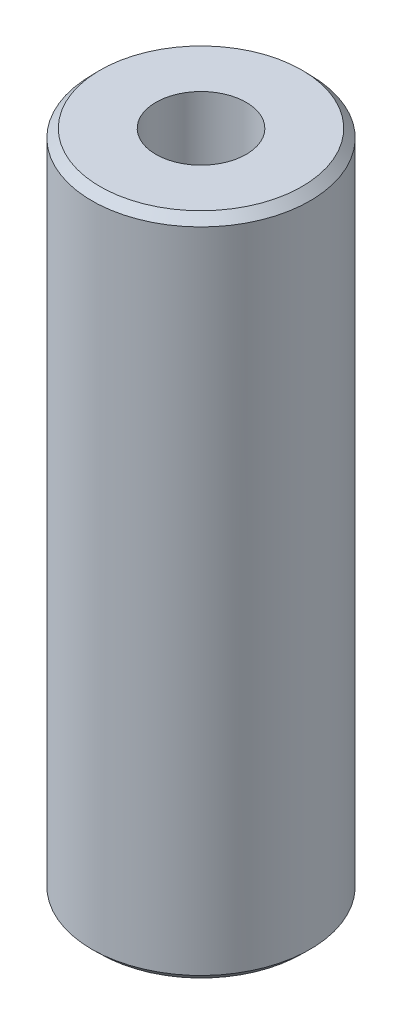
SolidWorks part; units mm, degrees
ref_plane "Front Plane" through (0, 0, 0) normal (0, 0, 1) x (1, 0, 0)
ref_plane "Top Plane" through (0, 0, 0) normal (0, 1, 0) x (1, 0, 0)
ref_plane "Right Plane" through (0, 0, 0) normal (1, 0, 0) x (0, 0, -1)
sketch "Sketch1" plane through (0, 0, 0) normal (0, 1, 0) x (1, 0, 0)
  circle A0 centre (0, 0) radius 20
  dimension "SHAFT_OD" = 40
extrude "Boss-Extrude1" add sketch "Sketch1" along normal blind 121.9242
sketch "Sketch2" plane through (0, 0, 0) normal (0, 1, 0) x (1, 0, 0)
  circle A0 centre (0, 0) radius 8.2842
  dimension "BORE_D" = 16.5684
extrude "Cut-Extrude1" cut sketch "Sketch2" along normal through all
chamfer "Chamfer1" distance 1.5249 angle 44.236 2 edges at (0, 121.9242, 20) (0, 0, 20) first distance on face at (0, 121.9242, 20) first distance on face at (0, 0, 8.2842)
